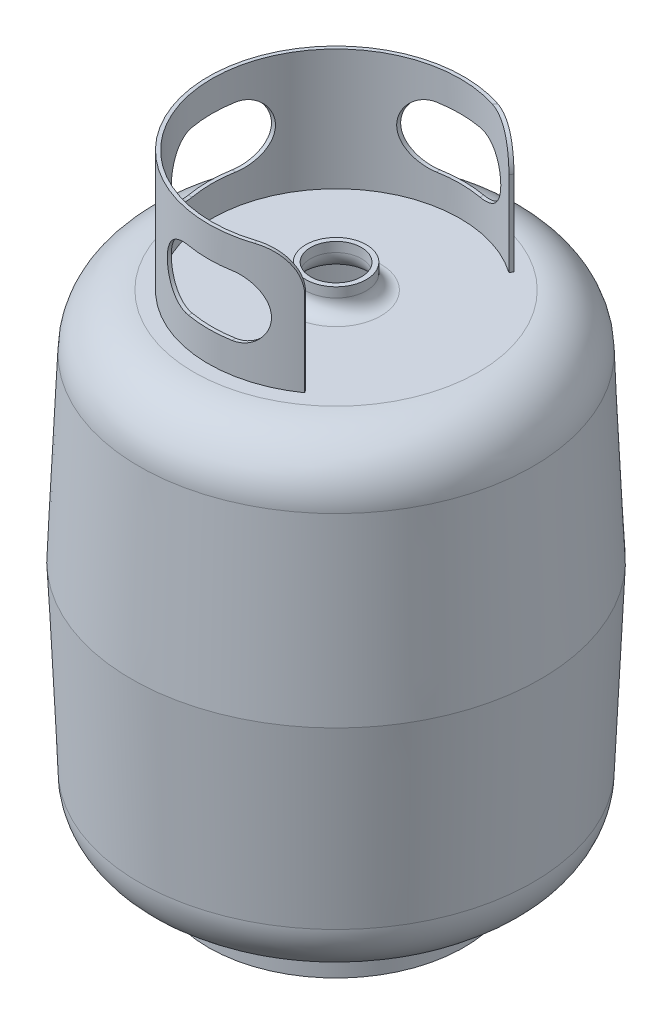
SolidWorks part; units mm, degrees
material "1060 Alloy"
ref_plane "Front Plane" through (0, 0, 0) normal (0, 0, 1) x (1, 0, 0)
ref_plane "Top Plane" through (0, 0, 0) normal (0, 1, 0) x (1, 0, 0)
ref_plane "Right Plane" through (0, 0, 0) normal (1, 0, 0) x (0, 0, -1)
sketch "Sketch1" plane through (0, 0, 0) normal (1, 0, 0) x (0, 0, -1)
  line L0 (0, -203.75) -> (0, 203.75) construction
  line L1 (-25, 203.75) -> (-25, 195.75)
  line L2 (-37, 183.75) -> (-117.5, 183.75)
  line L3 (-162.5, 138.75) -> (-168.9946, -10)
  line L4 (-168.9946, -10) -> (-162.5, -158.75)
  line L5 (-117.5, -203.75) -> (0, -203.75)
  line L13 (-21, 203.75) -> (-21, 195.75)
  line L14 (-37, 179.75) -> (-117.5, 179.75)
  line L15 (-158.4999, 138.6647) -> (-164.9908, -10)
  line L16 (-164.9908, -10) -> (-158.4999, -158.6647)
  line L17 (-117.5, -199.75) -> (0, -199.75)
  line L18 (-25, 203.75) -> (-21, 203.75)
  line L19 (0, -199.75) -> (0, -203.75)
  arc A0 (-25, 195.75) -> (-37, 183.75) centre (-37, 195.75) cw
  arc A1 (-117.5, 183.75) -> (-162.5, 138.75) centre (-117.5, 138.75) ccw
  arc A2 (-162.5, -158.75) -> (-117.5, -203.75) centre (-117.5, -158.75) ccw
  arc A6 (-21, 195.75) -> (-37, 179.75) centre (-37, 195.75) cw
  arc A7 (-117.5, 179.75) -> (-158.4999, 138.6647) centre (-117.5, 138.75) ccw
  arc A8 (-158.4999, -158.6647) -> (-117.5, -199.75) centre (-117.5, -158.75) ccw
  point P26 (0, 0)
  dimension "D2" = 12
  dimension "D3" = 45
  dimension "D1" = 20
  dimension "D4" = 92.5
  dimension "D5" = 387.5
  dimension "D6" = 92.5
  dimension "D7" = 50
  dimension "D8" = 325
  dimension "D9" = 4
revolve "Revolve1" add sketch "Sketch1" angle 360 about L0
sketch "Sketch2" plane through (0, 183.75, 0) normal (0, 1, 0) x (1, 0, 0)
  line L2 (58.7916, -83.9631) -> (60.5123, -86.4205)
  line L3 (58.7916, 83.9631) -> (60.5123, 86.4205)
  arc A0 (60.5123, -86.4205) -> (60.5123, 86.4205) centre (0, 0) cw
  circle A2 centre (0, 0) radius 117.5 construction
  arc A4 (58.7916, -83.9631) -> (58.7916, 83.9631) centre (0, 0) cw
  dimension "D2" = 12
  dimension "D1" = 3
  dimension "D3" = 110
extrude "Boss-Extrude1" add sketch "Sketch2" along normal blind 100
sketch "Sketch3" plane through (0, 0, 0) normal (0, 0, 1) x (1, 0, 0)
  line L0 (-18, 233.75) -> (18, 233.75) construction
  line L1 (-18, 258.75) -> (18, 258.75)
  line L2 (-18, 208.75) -> (18, 208.75)
  line L3 (0, 0) -> (0, 233.75) construction
  line L5 (60.5123, 283.75) -> (-105.5, 283.75) construction
  arc A0 (-18, 258.75) -> (-18, 208.75) centre (-18, 233.75) ccw
  arc A1 (18, 208.75) -> (18, 258.75) centre (18, 233.75) ccw
  point P2 (0, 233.75)
  dimension "D1" = 50
  dimension "D2" = 50
  dimension "D3" = 18
extrude "Cut-Extrude1" cut sketch "Sketch3" along normal up to next contours L1 A1 L2 A0
pattern_circular "CirPattern1" count 3 every 90 about axis through (0, 283.75, 0) along (0, -1, 0) of "Cut-Extrude1"
fillet "Fillet1" radius 30 2 edges at (59.6519, 283.75, -85.1918) (59.6519, 283.75, 85.1918)
sketch "Sketch4" plane through (0, -203.75, 0) normal (0, -1, 0) x (1, 0, 0)
  circle A1 centre (0, 0) radius 105.5
  circle A2 centre (0, 0) radius 117.5 construction
  circle A3 centre (0, 0) radius 102.5
  point P4 (0, 0)
  dimension "D1" = 12
  dimension "D2" = 3
extrude "Boss-Extrude2" add sketch "Sketch4" along normal blind 30
